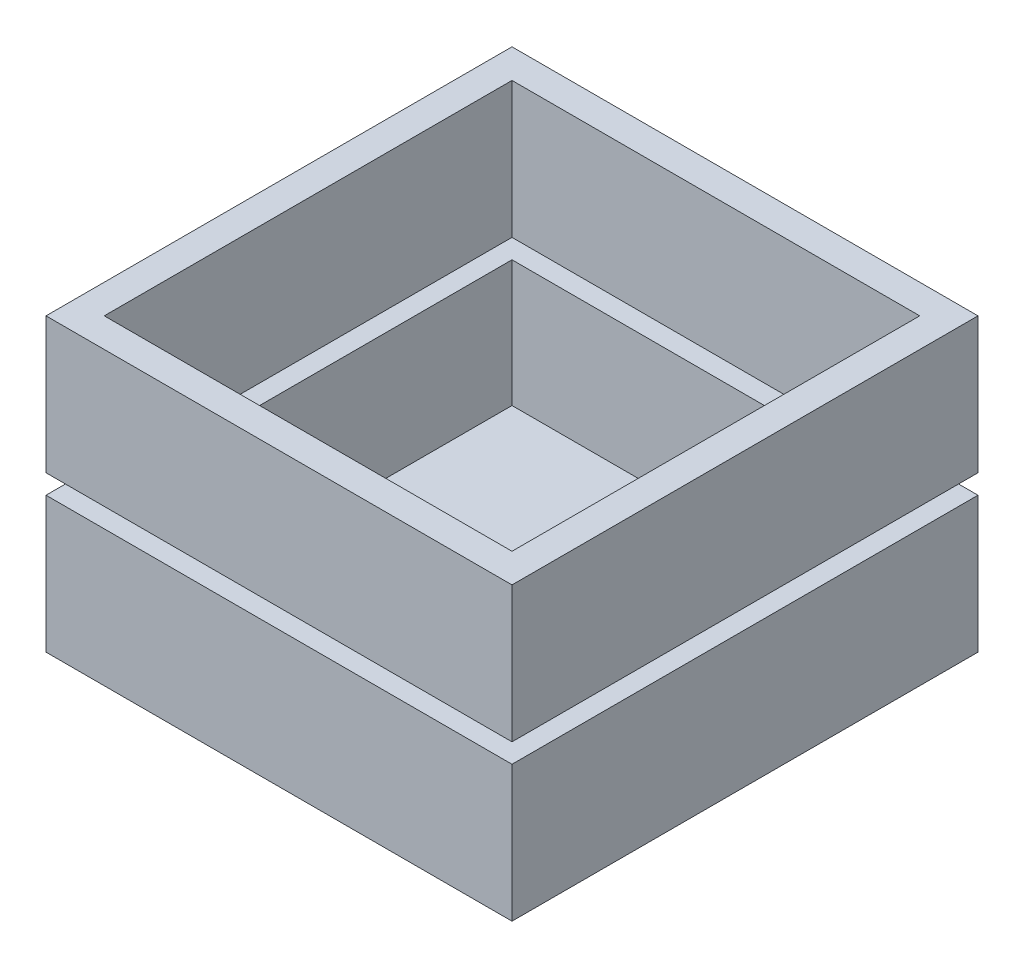
SolidWorks part; units mm, degrees
ref_plane "Front Plane" through (0, 0, 0) normal (0, 0, 1) x (1, 0, 0)
ref_plane "Top Plane" through (0, 0, 0) normal (0, 1, 0) x (1, 0, 0)
ref_plane "Right Plane" through (0, 0, 0) normal (1, 0, 0) x (0, 0, -1)
sketch "Sketch1" plane through (0, 0, 0) normal (0, 1, 0) x (1, 0, 0)
  line L1 (-152.4, 152.4) -> (152.4, 152.4)
  line L2 (-152.4, 152.4) -> (-152.4, -152.4)
  line L3 (-152.4, -152.4) -> (152.4, -152.4)
  line L4 (152.4, 152.4) -> (152.4, -152.4)
  line L5 (-152.4, 152.4) -> (152.4, -152.4) construction
  line L6 (-152.4, -152.4) -> (152.4, 152.4) construction
  point P0 (0, 0)
  dimension "D1" = 304.8
  dimension "D2" = 304.8
extrude "Boss-Extrude1" add sketch "Sketch1" along normal blind 203.2
shell "Shell1" thickness 19.05 removed face at (0, 203.2, 0)
sketch "Sketch2" plane through (0, 0, 152.4) normal (0, 0, 1) x (1, 0, 0)
  line L0 (-152.4, 203.2) -> (-152.4, 0) construction
  line L1 (-152.4, 114.3) -> (152.4, 114.3)
  line L2 (-152.4, 114.3) -> (-152.4, 101.6)
  line L3 (-152.4, 101.6) -> (152.4, 101.6)
  line L4 (152.4, 114.3) -> (152.4, 101.6)
  line L5 (152.4, 203.2) -> (152.4, 0) construction
  line L6 (-152.4, 203.2) -> (152.4, 203.2) construction
  line L7 (-152.4, 12.7) -> (152.4, 12.7)
  line L8 (-152.4, 12.7) -> (-152.4, 0)
  line L9 (-152.4, 0) -> (152.4, 0)
  line L10 (152.4, 12.7) -> (152.4, 0)
  dimension "D1" = 88.9
  dimension "D2" = 12.7
  dimension "D3" = 88.9
  dimension "D4" = 12.7
extrude "Cut-Extrude1" cut sketch "Sketch2" against normal through all
sketch "Sketch5" plane through (0, 0, 152.4) normal (0, 0, 1) x (1, 0, 0)
  line L0 (-228.6, 203.2) -> (-228.6, 0) construction
  line L1 (-228.6, 101.6) -> (228.6, 101.6)
  line L2 (-228.6, 101.6) -> (-228.6, 114.3)
  line L3 (-228.6, 114.3) -> (228.6, 114.3)
  line L4 (228.6, 101.6) -> (228.6, 114.3)
  line L5 (228.6, 203.2) -> (228.6, 0) construction
  line L6 (-228.6, 203.2) -> (228.6, 203.2) construction
  dimension "D1" = 88.9
  dimension "D2" = 12.7
extrude "Cut-Extrude2" [suppressed] cut sketch "Sketch5" against normal through all
sketch "Sketch6" [suppressed] plane through (0, 0, 0) normal (0, -1, 0) x (1, 0, 0)
  line L0 (-304.8, -209.55) -> (-304.8, 209.55) construction
  line L1 (-304.8, 120.65) -> (304.8, 120.65)
  line L2 (-304.8, 120.65) -> (-304.8, 101.6)
  line L3 (-304.8, 101.6) -> (304.8, 101.6)
  line L4 (304.8, 120.65) -> (304.8, 101.6)
  line L5 (304.8, 209.55) -> (304.8, -209.55) construction
  line L6 (-304.8, 209.55) -> (304.8, 209.55) construction
  line L7 (-304.8, 12.7) -> (304.8, 12.7)
  line L8 (-304.8, 12.7) -> (-304.8, -6.35)
  line L9 (-304.8, -6.35) -> (304.8, -6.35)
  line L10 (304.8, 12.7) -> (304.8, -6.35)
  line L11 (-304.8, -95.25) -> (304.8, -95.25)
  line L12 (-304.8, -95.25) -> (-304.8, -114.3)
  line L13 (-304.8, -114.3) -> (304.8, -114.3)
  line L14 (304.8, -95.25) -> (304.8, -114.3)
  line L15 (304.8, -209.55) -> (-304.8, -209.55) construction
  dimension "D1" = 88.9
  dimension "D2" = 19.05
  dimension "D3" = 88.9
  dimension "D4" = 19.05
  dimension "D5" = 88.9
  dimension "D6" = 19.05
  dimension "D7" = 95.25
extrude "Cut-Extrude3" [suppressed] cut sketch "Sketch6" against normal blind 19.05
sketch "Sketch7" plane through (0, 0, 0) normal (0, -1, 0) x (1, 0, 0)
  line L0 (-228.6, -209.55) -> (-228.6, 209.55) construction
  line L1 (-228.6, 120.65) -> (228.6, 120.65)
  line L2 (-228.6, 120.65) -> (-228.6, 101.6)
  line L3 (-228.6, 101.6) -> (228.6, 101.6)
  line L4 (228.6, 120.65) -> (228.6, 101.6)
  line L5 (228.6, 209.55) -> (228.6, -209.55) construction
  line L6 (-228.6, 209.55) -> (228.6, 209.55) construction
  line L7 (-228.6, 12.7) -> (228.6, 12.7)
  line L8 (-228.6, 12.7) -> (-228.6, -6.35)
  line L9 (-228.6, -6.35) -> (228.6, -6.35)
  line L10 (228.6, 12.7) -> (228.6, -6.35)
  line L11 (-228.6, -95.25) -> (228.6, -95.25)
  line L12 (-228.6, -95.25) -> (-228.6, -114.3)
  line L13 (-228.6, -114.3) -> (228.6, -114.3)
  line L14 (228.6, -95.25) -> (228.6, -114.3)
  dimension "D1" = 88.9
  dimension "D2" = 19.05
  dimension "D3" = 88.9
  dimension "D4" = 19.05
  dimension "D5" = 88.9
  dimension "D6" = 19.05
extrude "Cut-Extrude4" [suppressed] cut sketch "Sketch7" against normal blind 19.05
equation "\"D6@Sketch6\"=\"D2@Sketch6\""
equation "\"D4@Sketch6\"=\"D2@Sketch6\""
equation "\"D3@Sketch6\"=\"D1@Sketch6\""
equation "\"D5@Sketch6\"=\"D3@Sketch6\""
equation "\"D3@Sketch7\"=\"D1@Sketch7\""
equation "\"D4@Sketch7\"=\"D2@Sketch7\""
equation "\"D5@Sketch7\"=\"D1@Sketch7\""
equation "\"D6@Sketch7\"=\"D2@Sketch7\""
